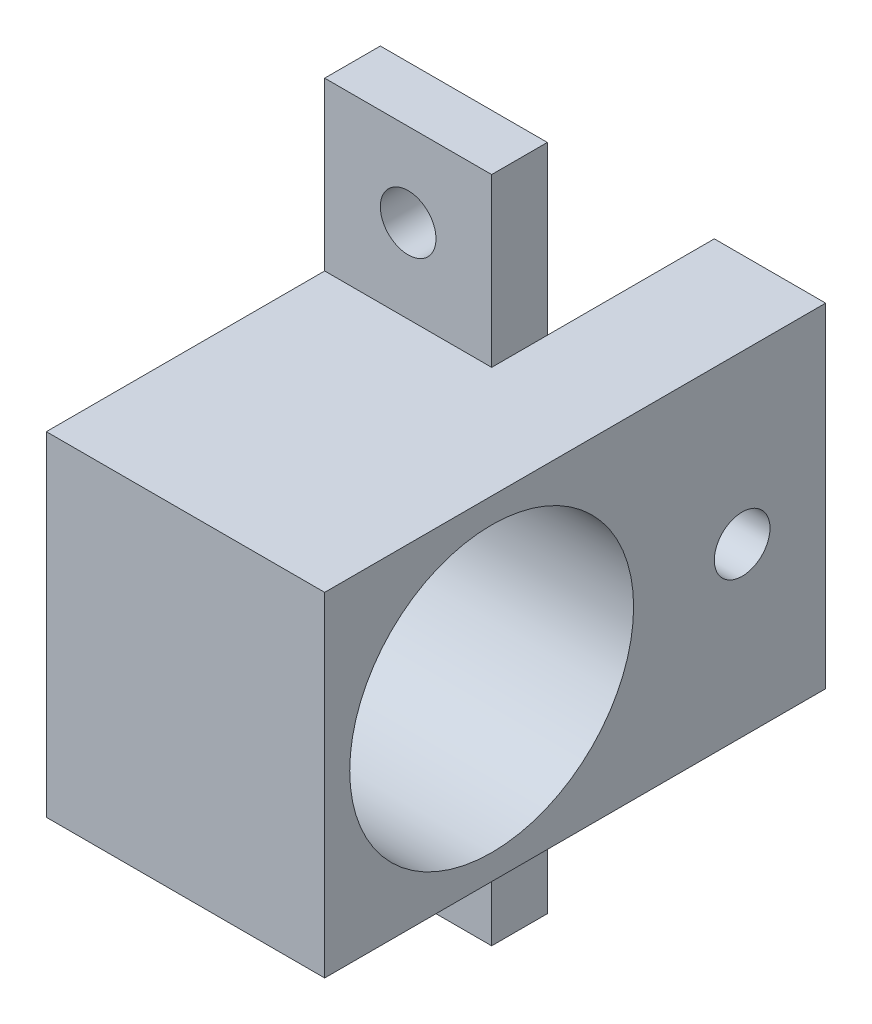
SolidWorks part; units mm, degrees
ref_plane "Front Plane" through (0, 0, 0) normal (1, 0, 0) x (0, 1, 0)
ref_plane "Top Plane" through (0, 0, 0) normal (0, 0, 1) x (0, 1, 0)
ref_plane "Right Plane" through (0, 0, 0) normal (0, 1, 0) x (-1, 0, 0)
sketch "Sketch1" plane through (0, 0, 0) normal (0, 0, 1) x (0, 1, 0)
  line L1 (0, 0) -> (30, 0)
  line L2 (0, 0) -> (0, 15)
  line L3 (0, 15) -> (30, 15)
  line L4 (30, 0) -> (30, 15)
  dimension "D1" = 15
  dimension "D2" = 30
extrude "Boss-Extrude1" add sketch "Sketch1" along normal blind 30 contours L1 L4 L3 L2
sketch "Sketch2" plane through (0, 0, 0) normal (1, 0, 0) x (0, 1, 0)
  line L1 (0, 30) -> (30, 30)
  line L2 (0, 30) -> (0, -15)
  line L3 (0, -15) -> (30, -15)
  line L4 (30, 30) -> (30, -15)
  line L6 (30, 30) -> (30, 0) construction
  line L7 (0, 0) -> (30, 0) construction
  point P7 (30, 0)
  dimension "D1" = 15
extrude "Boss-Extrude2" add sketch "Sketch2" along normal blind 10
sketch "Sketch3" plane through (10, 0, 0) normal (1, 0, 0) x (0, 1, 0)
  line L3 (30, 30) -> (0, 30) construction
  line L12 (15, 15) -> (15, 30)
  circle A2 centre (15, 15) radius 15
  circle A3 centre (15, 15) radius 12.75
  dimension "D1" = 30
sketch "Sketch5" plane through (10, 0, 0) normal (1, 0, 0) x (0, 1, 0)
  line L0 (0, 0) -> (30, 0) construction
  line L2 (30, -15) -> (30, 0) construction
  circle A0 centre (15, -7.5) radius 2.5
  dimension "D1" = 5
  dimension "D2" = 7.5
  dimension "D3" = 15
extrude "Cut-Extrude2" cut sketch "Sketch5" against normal through all
extrude "Cut-Extrude3" cut sketch "Sketch3" against normal through all contours A3
sketch "Sketch8" plane through (0, 0, 0) normal (0, 0, -1) x (1, 0, 0)
  line L0 (0, 0) -> (-15, 0) construction
  line L1 (-15, 0) -> (-15, -30) construction
  line L3 (-15, -30) -> (0, -30)
  line L4 (-15, -30) -> (-15, -45)
  line L5 (-15, -45) -> (0, -45)
  line L6 (0, -30) -> (0, -45)
  line L7 (-15, 0) -> (0, 0)
  line L8 (-15, 0) -> (-15, 15)
  line L9 (-15, 15) -> (0, 15)
  line L10 (0, 0) -> (0, 15)
  circle A0 centre (-7.5, -15) radius 2.5
  circle A1 centre (-7.5, -37.5) radius 2.5
  circle A2 centre (-7.5, 7.5) radius 2.5
  line M1 (0, 0) -> (-15, 0)
  line M3 (-15, -30) -> (0, -30)
  dimension "D1" = 5
  dimension "D4" = 5
  dimension "D5" = 5
  dimension "D2" = 15
  dimension "D3" = 7.5
  dimension "D6" = 15
  dimension "D7" = 15
  dimension "D8" = 7.5
  dimension "D9" = 7.5
extrude "Boss-Extrude4" add sketch "Sketch8" against normal blind 5 contours L6 L4 L5 A1 M3 | L10 L9 L8 A2 M1 region at (-7.5, 30.2121, 0) region at (-14.7879, -7.5, 0)
